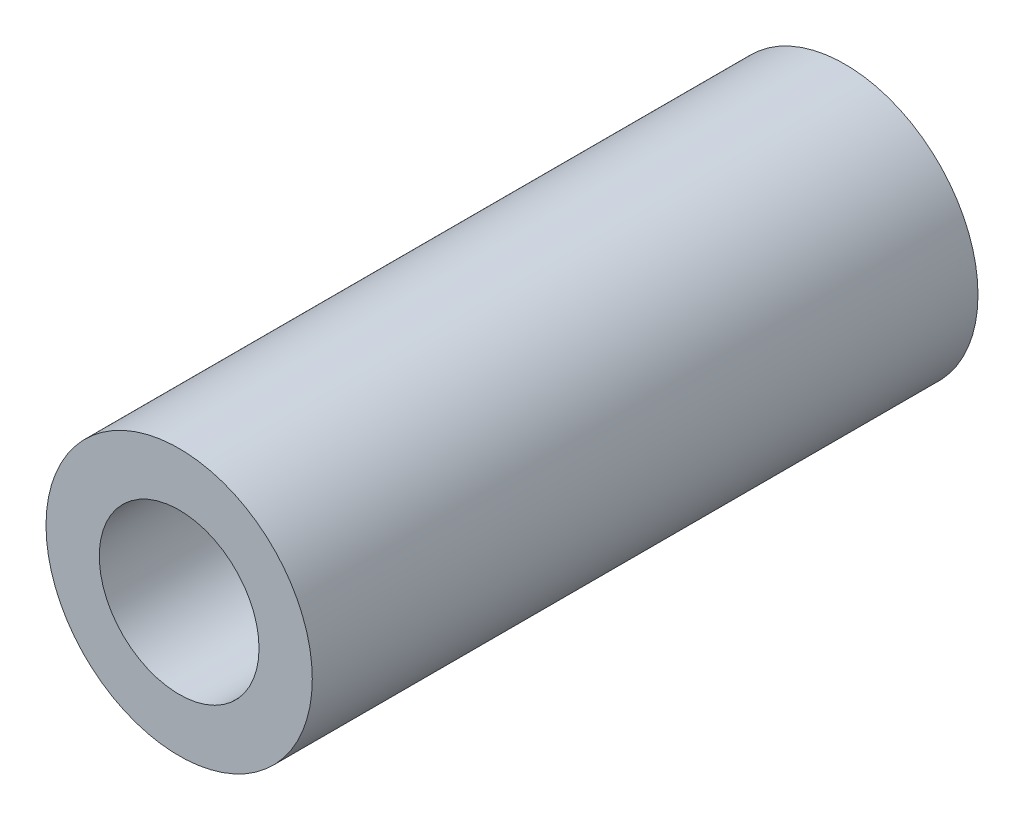
SolidWorks part; units mm, degrees
ref_plane "Front Plane" through (0, 0, 0) normal (0, 0, 1) x (1, 0, 0)
ref_plane "Top Plane" through (0, 0, 0) normal (0, 1, 0) x (1, 0, 0)
ref_plane "Right Plane" through (0, 0, 0) normal (1, 0, 0) x (0, 0, -1)
sketch "Sketch1" plane through (0, 0, 0) normal (0, 0, 1) x (1, 0, 0)
  circle A0 centre (0, 0) radius 5
  circle A1 centre (0, 0) radius 3
  dimension "D1" = 6
  dimension "D2" = 10
extrude "Boss-Extrude1" add sketch "Sketch1" along normal blind 25
